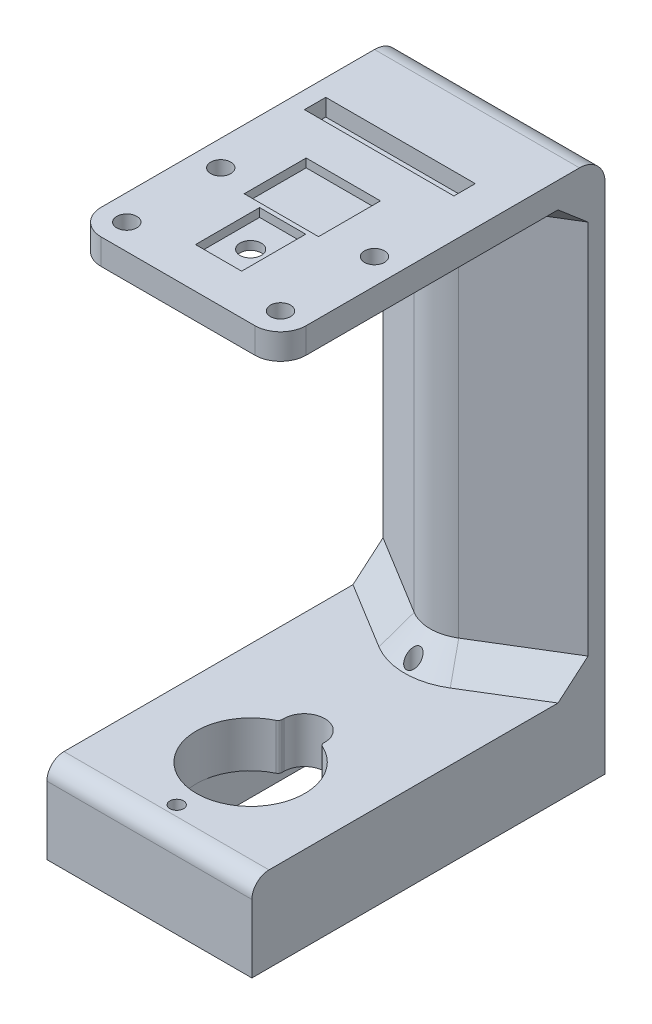
SolidWorks part; units mm, degrees
ref_plane "Front Plane" through (0, 0, 0) normal (0, 0, 1) x (1, 0, 0)
ref_plane "Top Plane" through (0, 0, 0) normal (0, 1, 0) x (1, 0, 0)
ref_plane "Right Plane" through (0, 0, 0) normal (1, 0, 0) x (0, 0, -1)
sketch "Sketch1" plane through (0, 0, 0) normal (0, 1, 0) x (1, 0, 0)
  line L0 (-8.3714, 14.5218) -> (-5.2417, 15.8503) construction
  line L1 (4.1328, 16.0958) -> (7.3278, 14.9329) construction
  line L2 (-2.3003, 10.2005) -> (-4.5861, 15.5854) construction
  line L3 (3.492, 15.7969) -> (1.4912, 10.2997) construction
  line L4 (11, 15.3) -> (-11, 15.3)
  line L5 (-11, 15.3) -> (-11, -12.7)
  line L6 (-11, -12.7) -> (11, -12.7)
  line L7 (11, -12.7) -> (11, 15.3)
  line L8 (11, 15.3) -> (-11, 15.3)
  line L9 (-11, 15.3) -> (-11, -12.7)
  line L10 (-11, -12.7) -> (11, -12.7)
  line L11 (11, -12.7) -> (11, 15.3)
  line L12 (2.58, -3.05) -> (-2.58, -3.05)
  line L13 (-2.58, -3.05) -> (-2.58, -7.35)
  line L14 (-2.58, -7.35) -> (2.58, -7.35)
  line L15 (2.58, -7.35) -> (2.58, -3.05)
  line L16 (2.58, -3.05) -> (-2.58, -3.05)
  line L17 (-2.58, -3.05) -> (-2.58, -7.35)
  line L18 (-2.58, -7.35) -> (2.58, -7.35)
  line L19 (2.58, -7.35) -> (2.58, -3.05)
  line L20 (-8.3714, 14.5218) -> (-5.2417, 15.8503)
  line L21 (4.1328, 16.0958) -> (7.3278, 14.9329)
  line L22 (-2.3003, 10.2005) -> (-4.5861, 15.5854)
  line L23 (3.492, 15.7969) -> (1.4912, 10.2997)
  line L24 (0, -5.2) -> (-13.371, 26.3)
  line L25 (0, -5.2) -> (11.4651, 26.3)
  line L26 (9.0061, 19.5441) -> (6.9918, 14.0099) construction
  line L27 (-5.7835, 8.425) -> (-7.9876, 13.6177) construction
  line L28 (2.3, 6.3) -> (-5, 6.3)
  line L29 (-5, 6.3) -> (-5, 3.8)
  line L30 (-5, 3.8) -> (2.3, 3.8)
  line L31 (2.3, 3.8) -> (2.3, 6.3)
  line L32 (2.3, 6.3) -> (-5, 6.3)
  line L33 (-5, 6.3) -> (-5, 3.8)
  line L34 (-5, 3.8) -> (2.3, 3.8)
  line L35 (2.3, 3.8) -> (2.3, 6.3)
  line L36 (10, 13.6) -> (-10, 13.6)
  line L37 (-10, 13.6) -> (-10, 8.6)
  line L38 (-10, 8.6) -> (10, 8.6)
  line L39 (10, 8.6) -> (10, 13.6)
  line L40 (10, 13.6) -> (-10, 13.6)
  line L41 (-10, 13.6) -> (-10, 8.6)
  line L42 (-10, 8.6) -> (10, 8.6)
  line L43 (10, 8.6) -> (10, 13.6)
  line L44 (-10.5, 26.3) -> (10.5, 26.3) construction
  circle A1 centre (-9, -10.7) radius 1.3
  circle A2 centre (-9, -10.7) radius 1.3
  circle A3 centre (9, -10.7) radius 1.3
  circle A4 centre (9, -10.7) radius 1.3
  circle A5 centre (-9, 0.3) radius 1.3
  circle A6 centre (-9, 0.3) radius 1.3
  circle A7 centre (9, 0.3) radius 1.3
  circle A8 centre (9, 0.3) radius 1.3
  circle A9 centre (0, -5.2) radius 3
  circle A10 centre (0, -5.2) radius 3
  dimension "D1" = 0
  dimension "D2" = 0
  dimension "D3" = 0
  dimension "D4" = 0
  dimension "D5" = 0
  dimension "D6" = 0
  dimension "D7" = 0
  dimension "D8" = 0
  dimension "D9" = 0
ref_plane "Plane1" through (0, 3, 0) normal (0, -1, 0) x (-1, 0, 0)
ref_plane "Plane2" through (0, 0, -24.3) normal (0, 0, 1) x (1, 0, 0)
sketch "Sketch2" plane through (0, 0, -24.3) normal (0, 0, 1) x (1, 0, 0)
  line L0 (-5.7, 0.5) -> (5.7, 0.5) construction
  line L1 (5.7, 0.5) -> (5.7, -46.5) construction
  line L2 (5.7, -46.5) -> (-5.7, -46.5) construction
  line L3 (-5.7, -46.5) -> (-5.7, 0.5) construction
  line L284 (0.8, -46.3) -> (0.8, -48.5)
  line L285 (-0.6, -46.1) -> (0.6, -46.1)
  line L286 (-0.8, -48.5) -> (-0.8, -46.3)
  line L287 (-1.74, -48.5) -> (-0.8, -48.5)
  line L288 (-1.74, -46.9) -> (-1.74, -48.5)
  line L289 (-3.34, -48.5) -> (-3.34, -46.9)
  line L290 (-10.5, -48.5) -> (-3.34, -48.5)
  line L291 (-10.5, -47.93) -> (-10.5, -48.5)
  line L292 (-8.9, -47.93) -> (-10.5, -47.93)
  line L293 (-10.5, -46.33) -> (-8.9, -46.33)
  line L294 (-10.5, -45.39) -> (-10.5, -46.33)
  line L295 (-8.9, -45.39) -> (-10.5, -45.39)
  line L296 (-10.5, -43.79) -> (-8.9, -43.79)
  line L297 (-10.5, -42.85) -> (-10.5, -43.79)
  line L298 (-8.3, -42.85) -> (-10.5, -42.85)
  line L299 (-8.1, -41.45) -> (-8.1, -42.65)
  line L300 (-10.5, -41.25) -> (-8.3, -41.25)
  line L301 (-10.5, -40.31) -> (-10.5, -41.25)
  line L302 (-8.9, -40.31) -> (-10.5, -40.31)
  line L303 (-10.5, -38.71) -> (-8.9, -38.71)
  line L304 (-10.5, -37.77) -> (-10.5, -38.71)
  line L305 (-8.9, -37.77) -> (-10.5, -37.77)
  line L306 (-10.5, -36.17) -> (-8.9, -36.17)
  line L307 (-10.5, -35.23) -> (-10.5, -36.17)
  line L308 (-8.9, -35.23) -> (-10.5, -35.23)
  line L309 (-10.5, -33.63) -> (-8.9, -33.63)
  line L310 (-10.5, -32.69) -> (-10.5, -33.63)
  line L311 (-8.9, -32.69) -> (-10.5, -32.69)
  line L312 (-10.5, -31.09) -> (-8.9, -31.09)
  line L313 (-10.5, -30.15) -> (-10.5, -31.09)
  line L314 (-8.3, -30.15) -> (-10.5, -30.15)
  line L315 (-8.1, -28.75) -> (-8.1, -29.95)
  line L316 (-10.5, -28.55) -> (-8.3, -28.55)
  line L317 (-10.5, -27.61) -> (-10.5, -28.55)
  line L318 (-8.9, -27.61) -> (-10.5, -27.61)
  line L319 (-10.5, -26.01) -> (-8.9, -26.01)
  line L320 (-10.5, -25.07) -> (-10.5, -26.01)
  line L321 (-8.9, -25.07) -> (-10.5, -25.07)
  line L322 (-10.5, -23.47) -> (-8.9, -23.47)
  line L323 (-10.5, -22.53) -> (-10.5, -23.47)
  line L324 (-8.9, -22.53) -> (-10.5, -22.53)
  line L325 (-10.5, -20.93) -> (-8.9, -20.93)
  line L326 (-10.5, -19.99) -> (-10.5, -20.93)
  line L327 (-8.9, -19.99) -> (-10.5, -19.99)
  line L328 (-10.5, -18.39) -> (-8.9, -18.39)
  line L329 (-10.5, -17.45) -> (-10.5, -18.39)
  line L330 (-8.3, -17.45) -> (-10.5, -17.45)
  line L331 (-8.1, -16.05) -> (-8.1, -17.25)
  line L332 (-10.5, -15.85) -> (-8.3, -15.85)
  line L333 (-10.5, -14.91) -> (-10.5, -15.85)
  line L334 (-8.9, -14.91) -> (-10.5, -14.91)
  line L335 (-10.5, -13.31) -> (-8.9, -13.31)
  line L336 (-10.5, -12.37) -> (-10.5, -13.31)
  line L337 (-8.9, -12.37) -> (-10.5, -12.37)
  line L338 (-10.5, -10.77) -> (-8.9, -10.77)
  line L339 (-10.5, -9.83) -> (-10.5, -10.77)
  line L340 (-8.9, -9.83) -> (-10.5, -9.83)
  line L341 (-10.5, -8.23) -> (-8.9, -8.23)
  line L342 (-10.5, -7.29) -> (-10.5, -8.23)
  line L343 (-8.9, -7.29) -> (-10.5, -7.29)
  line L344 (-10.5, -5.69) -> (-8.9, -5.69)
  line L345 (-10.5, -4.75) -> (-10.5, -5.69)
  line L346 (-8.3, -4.75) -> (-10.5, -4.75)
  line L347 (-8.1, -3.35) -> (-8.1, -4.55)
  line L348 (-10.5, -3.15) -> (-8.3, -3.15)
  line L349 (-10.5, -2.21) -> (-10.5, -3.15)
  line L350 (-8.9, -2.21) -> (-10.5, -2.21)
  line L351 (-10.5, -0.61) -> (-8.9, -0.61)
  line L352 (-10.5, 0.33) -> (-10.5, -0.61)
  line L353 (-8.9, 0.33) -> (-10.5, 0.33)
  line L354 (-10.5, 1.93) -> (-8.9, 1.93)
  line L355 (-10.5, 2.5) -> (-10.5, 1.93)
  line L356 (10.5, 2.5) -> (-10.5, 2.5)
  line L357 (10.5, 1.93) -> (10.5, 2.5)
  line L358 (8.9, 1.93) -> (10.5, 1.93)
  line L359 (10.5, 0.33) -> (8.9, 0.33)
  line L360 (10.5, -0.61) -> (10.5, 0.33)
  line L361 (8.9, -0.61) -> (10.5, -0.61)
  line L362 (10.5, -2.21) -> (8.9, -2.21)
  line L363 (10.5, -3.15) -> (10.5, -2.21)
  line L364 (8.3, -3.15) -> (10.5, -3.15)
  line L365 (8.1, -4.55) -> (8.1, -3.35)
  line L366 (10.5, -4.75) -> (8.3, -4.75)
  line L367 (10.5, -5.69) -> (10.5, -4.75)
  line L368 (8.9, -5.69) -> (10.5, -5.69)
  line L369 (10.5, -7.29) -> (8.9, -7.29)
  line L370 (10.5, -8.23) -> (10.5, -7.29)
  line L371 (8.9, -8.23) -> (10.5, -8.23)
  line L372 (10.5, -9.83) -> (8.9, -9.83)
  line L373 (10.5, -10.77) -> (10.5, -9.83)
  line L374 (8.9, -10.77) -> (10.5, -10.77)
  line L375 (10.5, -12.37) -> (8.9, -12.37)
  line L376 (10.5, -13.31) -> (10.5, -12.37)
  line L377 (8.9, -13.31) -> (10.5, -13.31)
  line L378 (10.5, -14.91) -> (8.9, -14.91)
  line L379 (10.5, -15.85) -> (10.5, -14.91)
  line L380 (8.3, -15.85) -> (10.5, -15.85)
  line L381 (8.1, -17.25) -> (8.1, -16.05)
  line L382 (10.5, -17.45) -> (8.3, -17.45)
  line L383 (10.5, -18.39) -> (10.5, -17.45)
  line L384 (8.9, -18.39) -> (10.5, -18.39)
  line L385 (10.5, -19.99) -> (8.9, -19.99)
  line L386 (10.5, -20.93) -> (10.5, -19.99)
  line L387 (8.9, -20.93) -> (10.5, -20.93)
  line L388 (10.5, -22.53) -> (8.9, -22.53)
  line L389 (10.5, -23.47) -> (10.5, -22.53)
  line L390 (8.9, -23.47) -> (10.5, -23.47)
  line L391 (10.5, -25.07) -> (8.9, -25.07)
  line L392 (10.5, -26.01) -> (10.5, -25.07)
  line L393 (8.9, -26.01) -> (10.5, -26.01)
  line L394 (10.5, -27.61) -> (8.9, -27.61)
  line L395 (10.5, -28.55) -> (10.5, -27.61)
  line L396 (8.3, -28.55) -> (10.5, -28.55)
  line L397 (8.1, -29.95) -> (8.1, -28.75)
  line L398 (10.5, -30.15) -> (8.3, -30.15)
  line L399 (10.5, -31.09) -> (10.5, -30.15)
  line L400 (8.9, -31.09) -> (10.5, -31.09)
  line L401 (10.5, -32.69) -> (8.9, -32.69)
  line L402 (10.5, -33.63) -> (10.5, -32.69)
  line L403 (8.9, -33.63) -> (10.5, -33.63)
  line L404 (10.5, -35.23) -> (8.9, -35.23)
  line L405 (10.5, -36.17) -> (10.5, -35.23)
  line L406 (8.9, -36.17) -> (10.5, -36.17)
  line L407 (10.5, -37.77) -> (8.9, -37.77)
  line L408 (10.5, -38.71) -> (10.5, -37.77)
  line L409 (8.9, -38.71) -> (10.5, -38.71)
  line L410 (10.5, -40.31) -> (8.9, -40.31)
  line L411 (10.5, -41.25) -> (10.5, -40.31)
  line L412 (8.3, -41.25) -> (10.5, -41.25)
  line L413 (8.1, -42.65) -> (8.1, -41.45)
  line L414 (10.5, -42.85) -> (8.3, -42.85)
  line L415 (10.5, -43.79) -> (10.5, -42.85)
  line L416 (8.9, -43.79) -> (10.5, -43.79)
  line L417 (10.5, -45.39) -> (8.9, -45.39)
  line L418 (10.5, -46.33) -> (10.5, -45.39)
  line L419 (8.9, -46.33) -> (10.5, -46.33)
  line L420 (10.5, -47.93) -> (8.9, -47.93)
  line L421 (10.5, -48.5) -> (10.5, -47.93)
  line L422 (3.34, -48.5) -> (10.5, -48.5)
  line L423 (3.34, -46.9) -> (3.34, -48.5)
  line L424 (1.74, -48.5) -> (1.74, -46.9)
  line L425 (0.8, -48.5) -> (1.74, -48.5)
  circle A4 centre (-5.7, -46.5) radius 1.05
  circle A5 centre (5.7, -46.5) radius 1.05
  circle A6 centre (-5.7, 0.5) radius 1.05
  circle A7 centre (5.7, 0.5) radius 1.05
  arc A112 (0.8, -46.3) -> (0.6, -46.1) centre (0.6, -46.3) ccw
  arc A113 (-0.6, -46.1) -> (-0.8, -46.3) centre (-0.6, -46.3) ccw
  arc A114 (-1.74, -46.9) -> (-3.34, -46.9) centre (-2.54, -46.9) ccw
  arc A115 (-8.9, -47.93) -> (-8.9, -46.33) centre (-8.9, -47.13) ccw
  arc A116 (-8.9, -45.39) -> (-8.9, -43.79) centre (-8.9, -44.59) ccw
  arc A117 (-8.3, -42.85) -> (-8.1, -42.65) centre (-8.3, -42.65) ccw
  arc A118 (-8.1, -41.45) -> (-8.3, -41.25) centre (-8.3, -41.45) ccw
  arc A119 (-8.9, -40.31) -> (-8.9, -38.71) centre (-8.9, -39.51) ccw
  arc A120 (-8.9, -37.77) -> (-8.9, -36.17) centre (-8.9, -36.97) ccw
  arc A121 (-8.9, -35.23) -> (-8.9, -33.63) centre (-8.9, -34.43) ccw
  arc A122 (-8.9, -32.69) -> (-8.9, -31.09) centre (-8.9, -31.89) ccw
  arc A123 (-8.3, -30.15) -> (-8.1, -29.95) centre (-8.3, -29.95) ccw
  arc A124 (-8.1, -28.75) -> (-8.3, -28.55) centre (-8.3, -28.75) ccw
  arc A125 (-8.9, -27.61) -> (-8.9, -26.01) centre (-8.9, -26.81) ccw
  arc A126 (-8.9, -25.07) -> (-8.9, -23.47) centre (-8.9, -24.27) ccw
  arc A127 (-8.9, -22.53) -> (-8.9, -20.93) centre (-8.9, -21.73) ccw
  arc A128 (-8.9, -19.99) -> (-8.9, -18.39) centre (-8.9, -19.19) ccw
  arc A129 (-8.3, -17.45) -> (-8.1, -17.25) centre (-8.3, -17.25) ccw
  arc A130 (-8.1, -16.05) -> (-8.3, -15.85) centre (-8.3, -16.05) ccw
  arc A131 (-8.9, -14.91) -> (-8.9, -13.31) centre (-8.9, -14.11) ccw
  arc A132 (-8.9, -12.37) -> (-8.9, -10.77) centre (-8.9, -11.57) ccw
  arc A133 (-8.9, -9.83) -> (-8.9, -8.23) centre (-8.9, -9.03) ccw
  arc A134 (-8.9, -7.29) -> (-8.9, -5.69) centre (-8.9, -6.49) ccw
  arc A135 (-8.3, -4.75) -> (-8.1, -4.55) centre (-8.3, -4.55) ccw
  arc A136 (-8.1, -3.35) -> (-8.3, -3.15) centre (-8.3, -3.35) ccw
  arc A137 (-8.9, -2.21) -> (-8.9, -0.61) centre (-8.9, -1.41) ccw
  arc A138 (-8.9, 0.33) -> (-8.9, 1.93) centre (-8.9, 1.13) ccw
  arc A139 (8.9, 1.93) -> (8.9, 0.33) centre (8.9, 1.13) ccw
  arc A140 (8.9, -0.61) -> (8.9, -2.21) centre (8.9, -1.41) ccw
  arc A141 (8.3, -3.15) -> (8.1, -3.35) centre (8.3, -3.35) ccw
  arc A142 (8.1, -4.55) -> (8.3, -4.75) centre (8.3, -4.55) ccw
  arc A143 (8.9, -5.69) -> (8.9, -7.29) centre (8.9, -6.49) ccw
  arc A144 (8.9, -8.23) -> (8.9, -9.83) centre (8.9, -9.03) ccw
  arc A145 (8.9, -10.77) -> (8.9, -12.37) centre (8.9, -11.57) ccw
  arc A146 (8.9, -13.31) -> (8.9, -14.91) centre (8.9, -14.11) ccw
  arc A147 (8.3, -15.85) -> (8.1, -16.05) centre (8.3, -16.05) ccw
  arc A148 (8.1, -17.25) -> (8.3, -17.45) centre (8.3, -17.25) ccw
  arc A149 (8.9, -18.39) -> (8.9, -19.99) centre (8.9, -19.19) ccw
  arc A150 (8.9, -20.93) -> (8.9, -22.53) centre (8.9, -21.73) ccw
  arc A151 (8.9, -23.47) -> (8.9, -25.07) centre (8.9, -24.27) ccw
  arc A152 (8.9, -26.01) -> (8.9, -27.61) centre (8.9, -26.81) ccw
  arc A153 (8.3, -28.55) -> (8.1, -28.75) centre (8.3, -28.75) ccw
  arc A154 (8.1, -29.95) -> (8.3, -30.15) centre (8.3, -29.95) ccw
  arc A155 (8.9, -31.09) -> (8.9, -32.69) centre (8.9, -31.89) ccw
  arc A156 (8.9, -33.63) -> (8.9, -35.23) centre (8.9, -34.43) ccw
  arc A157 (8.9, -36.17) -> (8.9, -37.77) centre (8.9, -36.97) ccw
  arc A158 (8.9, -38.71) -> (8.9, -40.31) centre (8.9, -39.51) ccw
  arc A159 (8.3, -41.25) -> (8.1, -41.45) centre (8.3, -41.45) ccw
  arc A160 (8.1, -42.65) -> (8.3, -42.85) centre (8.3, -42.65) ccw
  arc A161 (8.9, -43.79) -> (8.9, -45.39) centre (8.9, -44.59) ccw
  arc A162 (8.9, -46.33) -> (8.9, -47.93) centre (8.9, -47.13) ccw
  arc A163 (3.34, -46.9) -> (1.74, -46.9) centre (2.54, -46.9) ccw
ref_plane "Plane3" through (0, -50, 0) normal (0, 1, 0) x (1, 0, 0)
ref_plane "Plane4" through (0, -55.66, 0) normal (0, 1, 0) x (1, 0, 0)
ref_plane "Plane5" through (0, -57.16, 0) normal (0, 1, 0) x (1, 0, 0)
ref_plane "Plane6" through (0, -59.96, 0) normal (0, 1, 0) x (1, 0, 0)
ref_plane "Plane7" through (0, -8, 0) normal (0, 1, 0) x (1, 0, 0)
ref_axis "Axis2" through (-88.99, -8, -24.3) along (1, 0, 0)
sketch "Sketch4" plane through (0, -55.66, 0) normal (0, 1, 0) x (1, 0, 0)
  line L0 (-5.7, 11.4) -> (5.7, 11.4) construction
  line L1 (5.7, -11.4) -> (2.2271, -11.4) construction
  line L2 (-6.2, -2.9729) -> (-6.2, 10.9) construction
  line L3 (6.2, 10.9) -> (6.2, -2.9729) construction
  line L4 (-5.7, 11.4) -> (5.7, 11.4)
  line L5 (5.7, -11.4) -> (2.2271, -11.4)
  line L6 (-6.2, -2.9729) -> (-6.2, 10.9)
  line L7 (6.2, 10.9) -> (6.2, -2.9729)
sketch "Sketch5" plane through (0, -57.16, 0) normal (0, 1, 0) x (1, 0, 0)
  line L0 (6, -11.3899) -> (6, -15.85) construction
  line L1 (5.8, -16.05) -> (0.45, -16.05) construction
  line L2 (-6, -15.85) -> (-6, -11.3899) construction
  line L3 (-6, 11.3899) -> (-6, 15.85) construction
  line L4 (0.45, 16.05) -> (5.8, 16.05) construction
  line L5 (6, 15.85) -> (6, 11.3899) construction
  line L6 (6, -11.3899) -> (6, -15.85)
  line L7 (5.8, -16.05) -> (0.45, -16.05)
  line L8 (-6, -15.85) -> (-6, -11.3899)
  line L9 (-6, 11.3899) -> (-6, 15.85)
  line L10 (0.45, 16.05) -> (5.8, 16.05)
  line L11 (6, 15.85) -> (6, 11.3899)
  arc A0 (0.352, -14.4765) -> (-0.352, -14.4765) centre (0, -13.85) ccw construction
  arc A1 (-0.3628, 14.599) -> (0.3628, 14.599) centre (0, 13.85) ccw construction
  arc A2 (0.352, -14.4765) -> (-0.352, -14.4765) centre (0, -13.85) ccw
  arc A3 (-0.3628, 14.599) -> (0.3628, 14.599) centre (0, 13.85) ccw
sketch "Sketch6" plane through (0, 0, 0) normal (0, 1, 0) x (1, 0, 0)
  circle A0 centre (0, -5.2) radius 3 construction
  circle A1 centre (0, -5.2) radius 3 construction
  circle A2 centre (0, -5.2) radius 3.1 construction
  circle A3 centre (0, -5.2) radius 6
  dimension "D2" = 12
  dimension "D1" = 0.1
sketch "Sketch7" plane through (0, 3, 0) normal (0, -1, 0) x (-1, 0, 0)
  line L0 (11, -12.7) -> (-11, -12.7) construction
  line L1 (-11, -12.7) -> (-11, 15.3) construction
  line L2 (11, 15.3) -> (11, -12.7) construction
  line L3 (11, -12.7) -> (-11, -12.7) construction
  line L4 (-11, -12.7) -> (-11, 15.3) construction
  line L5 (11, 15.3) -> (11, -12.7) construction
  line L6 (-10.5, 24.3) -> (10.5, 24.3) construction
  line L7 (-10.5, 24.3) -> (10.5, 24.3) construction
  line L8 (-9, 1.475) -> (9, 1.475) construction
  line L9 (-12, 24.3) -> (12, 24.3)
  line L10 (-12, 24.3) -> (-12, -13.7)
  line L11 (-12, -13.7) -> (12, -13.7)
  line L12 (12, 24.3) -> (12, -13.7)
  line L13 (-9, -11.875) -> (9, -11.875) construction
  circle A0 centre (9, 0.3) radius 1.175
  circle A1 centre (9, -10.7) radius 1.175
  circle A2 centre (-9, -10.7) radius 1.175
  circle A3 centre (-9, 0.3) radius 1.175
  point P22 (-9, 1.475)
  point P23 (9, 1.475)
  point P24 (0, 24.3)
  point P28 (-9, -11.875)
  point P29 (0, 0)
  point P33 (9, -11.875)
  dimension "D1" = 2.35
  dimension "D2" = 1
  dimension "D3" = 1
extrude "Boss-Extrude1" add sketch "Sketch7" along normal blind 3
sketch "Sketch11" plane through (0, 3, 0) normal (0, 1, 0) x (1, 0, 0)
  line L0 (-5, 6.3) -> (-5, 3.8) construction
  line L1 (2.3, 3.8) -> (2.3, 6.3) construction
  line L2 (-5, 3.8) -> (2.3, 3.8) construction
  line L3 (2.3, 6.3) -> (-5, 6.3) construction
  line L4 (-5, 6.3) -> (-5, 3.8) construction
  line L5 (2.3, 3.8) -> (2.3, 6.3) construction
  line L6 (-5, 3.8) -> (2.3, 3.8) construction
  line L7 (2.3, 6.3) -> (-5, 6.3) construction
  line L8 (-10, 13.6) -> (-10, 8.6) construction
  line L9 (-10, 13.6) -> (7.5, 13.6)
  line L10 (-10, 13.6) -> (-10, 11.1)
  line L11 (-10, 11.1) -> (7.5, 11.1)
  line L12 (7.5, 13.6) -> (7.5, 11.1)
  line L13 (-10, 13.6) -> (-10, 8.6) construction
  line L14 (10, 13.6) -> (-10, 13.6) construction
  line L16 (10, 8.6) -> (10, 13.6) construction
  point P12 (-10, 11.1)
  dimension "D1" = 2.5
extrude "Cut-Extrude3" cut sketch "Sketch11" against normal blind 2
ref_axis "Axis1" through (88.99, -59.96, -24.3) along (-1, 0, 0)
sketch "Sketch8" plane through (0, 0, 0) normal (0, -1, 0) x (1, 0, 0)
  circle A0 centre (0, 5.2) radius 3.1 construction
  circle A1 centre (0, 5.2) radius 3.1
extrude "Cut-Extrude1" cut sketch "Sketch8" against normal blind 1
sketch "Sketch9" plane through (0, 3, 0) normal (0, 1, 0) x (1, 0, 0)
  line L0 (2.3, 6.3) -> (-5, 6.3) construction
  line L1 (-2.7, -1.45) -> (2.7, -1.45)
  line L2 (-2.7, -1.45) -> (-2.7, -8.95)
  line L3 (-2.7, -8.95) -> (2.7, -8.95)
  line L4 (2.7, -1.45) -> (2.7, -8.95)
  line L5 (-2.7, -1.45) -> (2.7, -8.95) construction
  line L6 (-2.7, -8.95) -> (2.7, -1.45) construction
  line L7 (-2.7, 3.05) -> (2.7, 3.05) construction
  line L8 (-2.7, 3.05) -> (-2.7, -0.95) construction
  line L9 (-2.7, -0.95) -> (2.7, -0.95) construction
  line L10 (2.7, 3.05) -> (2.7, -0.95) construction
  line L11 (-2.7, 3.05) -> (2.7, -0.95) construction
  line L12 (-2.7, -0.95) -> (2.7, 3.05) construction
  line L13 (-5, 6.3) -> (3.7, 6.3)
  line L14 (-5, 6.3) -> (-5, -0.95)
  line L15 (-5, -0.95) -> (3.7, -0.95)
  line L16 (3.7, 6.3) -> (3.7, -0.95)
  line L17 (-5, 6.3) -> (-5, 3.8) construction
  point P0 (0, -5.2)
  point P6 (0, 1.05)
  dimension "D1" = 5.4
  dimension "D2" = 7.5
  dimension "D3" = 0.5
  dimension "D4" = 4
  dimension "D5" = 1
extrude "Cut-Extrude2" cut sketch "Sketch9" against normal blind 1
sketch "Sketch12" plane through (0, 0, -24.3) normal (0, 0, 1) x (1, 0, 0)
  line L0 (3.34, -48.5) -> (10.5, -48.5) construction
  line L1 (10.5, 2.5) -> (8.1, 2.5)
  line L2 (10.5, 2.5) -> (10.5, -48.5)
  line L3 (10.5, -48.5) -> (8.1, -48.5)
  line L4 (12, 3) -> (-12, 3)
  line L5 (12, 0) -> (12, 3)
  line L6 (-12, 0) -> (12, 0)
  line L7 (-12, 3) -> (-12, 0)
  line L8 (12, 3) -> (-12, 3)
  line L9 (12, 0) -> (12, 3)
  line L10 (-12, 0) -> (12, 0)
  line L11 (-12, 3) -> (-12, 0)
  line L12 (8.1, 2.5) -> (8.1, -48.5)
  line L13 (10.5, 2.5) -> (-10.5, 2.5) construction
  line L14 (-10.5, -48.5) -> (-8.1, -48.5)
  line L15 (-10.5, -48.5) -> (-10.5, 2.5)
  line L16 (-10.5, 2.5) -> (-8.1, 2.5)
  line L17 (-8.1, -48.5) -> (-8.1, 2.5)
  circle A0 centre (-5.7, -46.5) radius 1.05 construction
  circle A1 centre (5.7, -46.5) radius 1.05 construction
  circle A2 centre (5.7, 0.5) radius 1.05 construction
  circle A3 centre (-5.7, 0.5) radius 1.05 construction
  circle A4 centre (-5.7, -46.5) radius 1.05
  circle A5 centre (5.7, -46.5) radius 1.05
  circle A6 centre (5.7, 0.5) radius 1.05
  circle A7 centre (-5.7, 0.5) radius 1.05
  arc A8 (8.9, -43.79) -> (8.9, -45.39) centre (8.9, -44.59) ccw construction
  arc A9 (-8.9, 0.33) -> (-8.9, 1.93) centre (-8.9, 1.13) ccw construction
  dimension "D1" = 0
sketch "Sketch13" plane through (0, 0, -24.3) normal (0, 0, 1) x (1, 0, 0)
  line L0 (88.99, -59.96) -> (-88.99, -59.96) construction
  line L1 (-12, 3) -> (12, 3)
  line L2 (-12, 3) -> (-12, -59.96)
  line L3 (-12, -59.96) -> (12, -59.96)
  line L4 (12, 3) -> (12, -59.96)
  line L5 (12, 0) -> (12, 3) construction
extrude "Boss-Extrude4" add sketch "Sketch13" along normal blind 2
sketch "Sketch14" plane through (0, 0, 0) normal (0, -1, 0) x (1, 0, 0)
  line L0 (0, 13.7) -> (0, -22.3) construction
  line L1 (12, 13.7) -> (-12, 13.7) construction
  line L2 (-12, -22.3) -> (12, -22.3) construction
  line L3 (-12, -22.3) -> (0, -14.9613)
  line L4 (0, -14.9613) -> (12, -22.3)
  line L5 (0, -13.7892) -> (-12, -21.1278) construction
  line L6 (-12, 13.7) -> (-12, -22.3) construction
  line L7 (0, -13.7892) -> (12, -21.1278) construction
  line L8 (12, -22.3) -> (12, 13.7) construction
  line L9 (3.492, -15.7969) -> (1.4912, -10.2997) construction
  line L10 (4.1328, -16.0958) -> (7.3278, -14.9329) construction
  line L11 (3.9618, -15.6259) -> (4.1328, -16.0958) construction
  line L12 (3.9618, -15.6259) -> (3.492, -15.7969) construction
  line L13 (-12, -22.3) -> (12, -22.3)
  circle A0 centre (3.9618, -15.6259) radius 0.5 construction
  dimension "D1" = 1
extrude "Boss-Extrude5" add sketch "Sketch14" along normal up to surface (50 mm away) up to plane "Plane3"
fillet "Fillet1" radius 3 2 edges at (-12, 1.5, 13.7) (12, 1.5, 13.7)
sketch "Sketch20" plane through (0, -50, 0) normal (0, 1, 0) x (1, 0, 0)
  arc A0 (2.175, 1.1595) -> (-2.325, 1.1595) centre (-0.075, 1.1595) ccw construction
  arc A1 (-6.2, -5.2) -> (1.9133, 0.6974) centre (0, -5.2) ccw construction
  arc A2 (2.175, 1.1595) -> (-2.325, 1.1595) centre (-0.075, 1.1595) ccw
  arc A3 (-6.2, -5.2) -> (1.9133, 0.6974) centre (0, -5.2) ccw
sketch "Sketch30" plane through (0, 0, 0) normal (0, -1, 0) x (1, 0, 0)
  line L0 (-3.1, 5.2) -> (-3.5, 5.2) construction
  line L1 (3.1, 5.2) -> (3.5, 5.2) construction
  line L2 (-3.5, 5.2) -> (-2.7457, 6.6391)
  line L3 (-3.5, 5.2) -> (-2.7457, 3.7609)
  line L4 (3.5, 5.2) -> (2.7457, 6.6391)
  line L5 (3.5, 5.2) -> (2.7457, 3.7609)
  arc A1 (-2.7457, 6.6391) -> (-2.7457, 3.7609) centre (0, 5.2) ccw
  arc A2 (2.7457, 3.7609) -> (2.7457, 6.6391) centre (0, 5.2) ccw
  circle A3 centre (0, 5.2) radius 3.1 construction
  point P4 (3.1, 5.2)
  dimension "D1" = 0.4
extrude "Cut-Extrude13" cut sketch "Sketch30" against normal up to surface (1 mm away) up to face at (0, 1, 2.1)
sketch "Sketch21" plane through (0, -50, 0) normal (0, 1, 0) x (1, 0, 0)
  line L0 (-12, -10.7) -> (-12, 24.3) construction
  line L1 (12, 24.3) -> (12, -10.7) construction
  line L2 (-12, -10.7) -> (-12, 24.3) construction
  line L3 (12, 24.3) -> (12, -10.7) construction
  line L4 (5.8, -16.05) -> (0.45, -16.05) construction
  line L5 (5.8, -16.05) -> (0.45, -16.05) construction
  line L6 (12, 22.3) -> (-12, 22.3) construction
  line L7 (-12, -17.05) -> (12, -17.05)
  line L8 (-12, -17.05) -> (-12, 22.3)
  line L9 (-12, 22.3) -> (12, 22.3)
  line L10 (12, -17.05) -> (12, 22.3)
  dimension "D1" = 1
extrude "Boss-Extrude8" add sketch "Sketch21" against normal up to surface (9.96 mm away) up to plane "Plane6"
sketch "Sketch22" plane through (0, -50, 0) normal (0, 1, 0) x (1, 0, 0)
  line L0 (-2.475, 1.1595) -> (-2.475, 0.6478)
  line L1 (2.325, 1.1595) -> (2.325, 0.7091)
  arc A0 (-2.475, 0.6478) -> (2.325, 0.7091) centre (0, -5.2) ccw
  arc A1 (2.325, 1.1595) -> (-2.475, 1.1595) centre (-0.075, 1.1595) ccw
  arc A2 (2.175, 1.1595) -> (-2.325, 1.1595) centre (-0.075, 1.1595) ccw construction
  arc A3 (-6.2, -5.2) -> (1.9133, 0.6974) centre (0, -5.2) ccw construction
  arc A4 (2.175, 1.1595) -> (-2.325, 1.1595) centre (-0.075, 1.1595) ccw construction
  arc A5 (-6.2, -5.2) -> (1.9133, 0.6974) centre (0, -5.2) ccw construction
  dimension "D1" = 0.15
  dimension "D2" = 0.15
extrude "Cut-Extrude7" cut sketch "Sketch22" against normal through all
fillet "Fillet2" radius 0.5 2 edges at (2.325, -54.98, -0.7091) (-2.475, -54.98, -0.6478)
sketch "Sketch23" plane through (0, -55.66, 0) normal (0, 1, 0) x (1, 0, 0)
  line L0 (-5.7, 11.4) -> (5.7, 11.4) construction
  line L1 (-6.2, 11.4) -> (6.2, 11.4) construction
  line L2 (-6.2, 11.4) -> (-6.2, -11.4) construction
  line L3 (-6.2, -11.4) -> (6.2, -11.4) construction
  line L4 (6.2, 11.4) -> (6.2, -11.4) construction
  line L5 (5.7, -11.4) -> (2.2271, -11.4) construction
  line L6 (6.2, 10.9) -> (6.2, -2.9729) construction
  line L7 (-6.2, -2.9729) -> (-6.2, 10.9) construction
  line L8 (-6.35, 11.55) -> (-6.35, -11.55)
  line L9 (-6.35, -11.55) -> (6.35, -11.55)
  line L10 (6.35, 11.55) -> (6.35, -11.55)
  line L11 (-6.35, 11.55) -> (6.35, 11.55)
  dimension "D1" = 0.15
extrude "Cut-Extrude8" cut sketch "Sketch23" against normal through all from offset 0.3
sketch "Sketch24" plane through (0, -57.16, 0) normal (0, 1, 0) x (1, 0, 0)
  line L0 (0.45, 16.05) -> (5.8, 16.05) construction
  line L1 (-6, 16.05) -> (6, 16.05) construction
  line L2 (-6, 16.05) -> (-6, -16.05) construction
  line L3 (-6, -16.05) -> (6, -16.05) construction
  line L4 (6, 16.05) -> (6, -16.05) construction
  line L5 (5.8, -16.05) -> (0.45, -16.05) construction
  line L6 (6, 15.85) -> (6, 11.3899) construction
  line L7 (-6, 11.3899) -> (-6, 15.85) construction
  line L8 (-6.15, 16.2) -> (-6.15, -16.2)
  line L9 (-6.15, -16.2) -> (6.15, -16.2)
  line L10 (6.15, 16.2) -> (6.15, -16.2)
  line L11 (-6.15, 16.2) -> (6.15, 16.2)
  dimension "D1" = 0.15
extrude "Cut-Extrude9" cut sketch "Sketch24" against normal through all from offset 0.3
sketch "Sketch25" plane through (0, -56.86, 0) normal (0, -1, 0) x (1, 0, 0)
  circle A0 centre (0, 13.85) radius 0.8
  circle A1 centre (0, -13.85) radius 0.8
  dimension "D1" = 1.6
extrude "Cut-Extrude10" cut sketch "Sketch25" against normal up to next
fillet "Fillet6" radius 2 1 edges at (0, -50, 17.05)
sketch "Sketch27" plane through (0, 0, -24.3) normal (0, 0, -1) x (-1, 0, 0)
  line L0 (12, -59.96) -> (12, 3) construction
  line L1 (-5.7, -4.98) -> (5.7, -4.98) construction
  line L2 (-5.7, -4.98) -> (-5.7, -51.98) construction
  line L3 (-5.7, -51.98) -> (5.7, -51.98) construction
  line L4 (5.7, -4.98) -> (5.7, -51.98) construction
  line L5 (5.7, -46.5) -> (5.7, 0.5) construction
  line L6 (5.7, 0.5) -> (-5.7, 0.5) construction
  circle A0 centre (5.7, -4.98) radius 2
  circle A1 centre (-5.7, -4.98) radius 2
  circle A2 centre (-5.7, -51.98) radius 2
  circle A3 centre (5.7, -51.98) radius 2
  point P4 (0, -4.98)
  point P8 (12, -28.48)
  point P9 (5.7, -28.48)
  dimension "D1" = 4
extrude "Boss-Extrude9" add sketch "Sketch27" along normal blind 2
chamfer "Chamfer4" distance 2 angle 45 4 edges at (-3.7, -51.98, -24.3) (7.7, -51.98, -24.3) (7.7, -4.98, -24.3) (-3.7, -4.98, -24.3)
sketch "Sketch28" plane through (0, 0, -26.3) normal (0, 0, -1) x (-1, 0, 0)
  circle A0 centre (5.7, -4.98) radius 0.9
  circle A1 centre (-5.7, -4.98) radius 0.9
  circle A2 centre (-5.7, -51.98) radius 0.9
  circle A3 centre (5.7, -51.98) radius 0.9
  dimension "D1" = 1.8
extrude "Cut-Extrude11" cut sketch "Sketch28" against normal blind 6
sketch "Sketch29" plane through (0, -59.96, 0) normal (0, -1, 0) x (1, 0, 0)
  line L0 (6.35, 0) -> (12, 0) construction
  line L1 (6.35, 11.55) -> (6.35, -11.55) construction
  line L2 (12, 17.05) -> (12, -24.3) construction
  line L3 (-6.35, 0) -> (-12, 0) construction
  line L4 (-6.35, -11.55) -> (-6.35, 11.55) construction
  line L5 (-12, 17.05) -> (-12, -24.3) construction
  line L6 (9.175, 17.05) -> (9.175, -24.3) construction
  line L7 (-12, 17.05) -> (12, 17.05) construction
  line L8 (1.7, -24.3) -> (9.7, -24.3) construction
  line L9 (-9.175, 17.05) -> (-9.175, -24.3) construction
  line L10 (-9.7, -24.3) -> (-1.7, -24.3) construction
  line L11 (-9.175, 17.05) -> (-9.175, 14.225) construction
  line L12 (-9.175, 0) -> (-12, 0) construction
  line L13 (-9.175, -21.475) -> (-9.175, -24.3) construction
  circle A0 centre (9.175, 14.225) radius 1.425
  circle A1 centre (-9.175, 14.225) radius 1.425
  circle A2 centre (-9.175, -21.475) radius 1.425
  circle A3 centre (9.175, -21.475) radius 1.425
  point P19 (9.175, 0)
  point P24 (-9.175, 0)
  dimension "D1" = 2.85
extrude "Cut-Extrude12" cut sketch "Sketch29" against normal offset from surface (7.96 mm away) 2 up to face at (0, -50, 13.05)
fillet "Fillet7" radius 5 1 edges at (0, -25, -14.9613)
chamfer "Chamfer5" distance 3 angle 45 6 edges at (7.3043, -50, -19.4283) (0, -50, -15.8222) (-7.3043, -50, -19.4283) (7.3043, 0, -19.4283) (0, 0, -15.8222) (-7.3043, 0, -19.4283)
fillet "Fillet8" radius 3 1 edges at (0, 3, -24.3)
sketch "Sketch31" plane through (0, 2, 0) normal (0, 1, 0) x (1, 0, 0)
  circle A0 centre (0, -5.2) radius 1.25
  dimension "D1" = 2.5
extrude "Cut-Extrude14" cut sketch "Sketch31" against normal up to next
